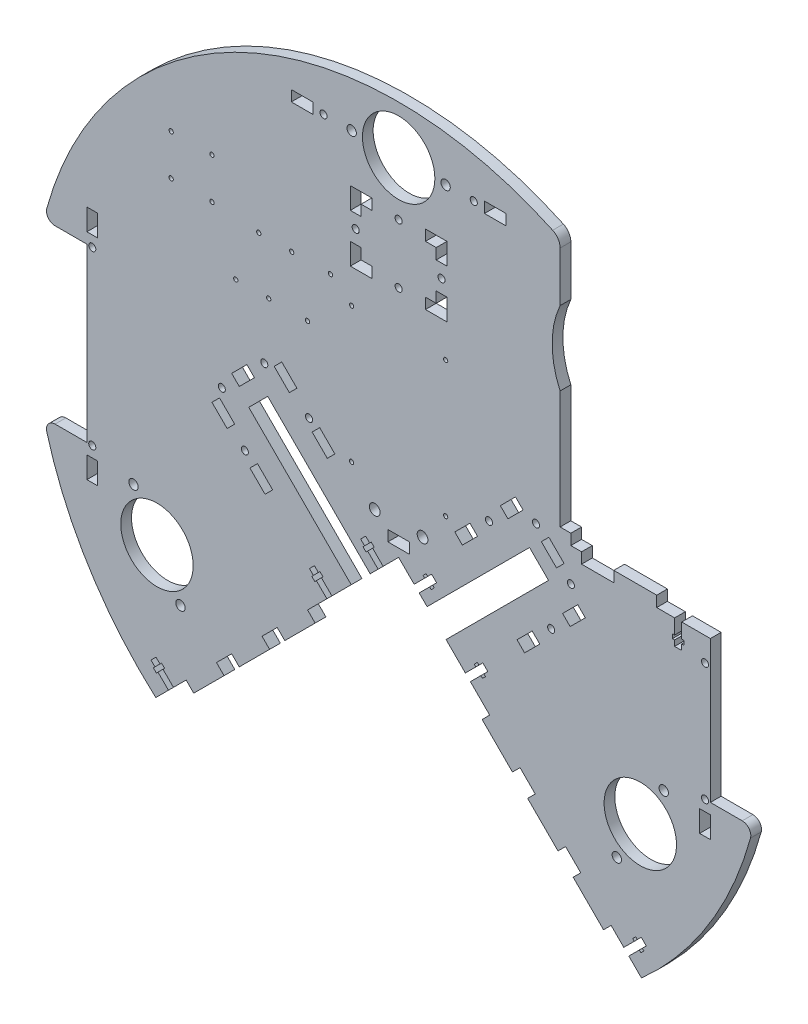
SolidWorks part; units mm, degrees
ref_plane "Front Plane" through (0, 0, 0) normal (0, 0, 1) x (1, 0, 0)
ref_plane "Top Plane" through (0, 0, 0) normal (0, 1, 0) x (1, 0, 0)
ref_plane "Right Plane" through (0, 0, 0) normal (1, 0, 0) x (0, 0, -1)
sketch "Sketch1" plane through (0, 0, 0) normal (0, 0, 1) x (1, 0, 0)
  circle A0 centre (0, 0) radius 215.9
  dimension "D1" = 431.8
extrude "Base Plate Extrusion" add sketch "Sketch1" along normal blind 6.35
sketch "Sketch2" plane through (0, 0, 6.35) normal (0, 0, 1) x (1, 0, 0)
  line L0 (0, 0) -> (0, -230.9791) construction
  line L1 (0, -17.4608) -> (143.6841, -161.1449)
  line L2 (0, -17.4608) -> (-143.6841, -161.1449)
  circle A1 centre (0, 0) radius 215.9 construction
  arc A2 (143.6841, -161.1449) -> (-143.6841, -161.1449) centre (0, 0) cw
  dimension "D1" = 90
  dimension "D2" = 203.2
extrude "V Funnel Cut" cut sketch "Sketch2" against normal through all
sketch "Sketch3" plane through (0, 0, 6.35) normal (0, 0, 1) x (1, 0, 0)
  line L0 (0, 0) -> (251.7982, 0) construction
  line L1 (209.8384, 50.8) -> (184.4384, 50.8)
  line L2 (209.8384, 50.8) -> (209.8384, -50.8)
  line L3 (209.8384, -50.8) -> (184.4384, -50.8)
  line L4 (184.4384, 50.8) -> (184.4384, -50.8)
  arc A0 (143.6841, -161.1449) -> (-143.6841, -161.1449) centre (0, 0) ccw construction
  arc A1 (209.8384, 50.8) -> (209.8384, -50.8) centre (0, 0) cw
  arc M7 (143.6841, -161.1449) -> (-143.6841, -161.1449) centre (0, 0) ccw
  dimension "D1" = 25.4
  dimension "D2" = 101.6
extrude "Wheel Track Cut" cut sketch "Sketch3" against normal through all contours L2 L0 A1 | L4 L0 L2 L1 | L0 L4 L3 L2 | L0 L2 M7 region at (197.1384, 25.4, 6.35) region at (197.1384, -25.4, 6.35) region at (212.266, 19.0862, 6.35) region at (212.266, -19.0862, 6.35)
mirror "Wheel Track Cut Mirror" about plane through (0, 0, 0) normal (1, 0, 0) of "Wheel Track Cut"
sketch "Sketch4" plane through (0, 0, 6.35) normal (0, 0, 1) x (1, 0, 0)
  line L0 (88.68, 15.0926) -> (77.4547, 26.3179)
  line L1 (88.68, 15.0926) -> (28.0633, -45.5241)
  line L2 (77.4547, 26.3179) -> (16.838, -34.2988)
  line L3 (28.0633, -45.5241) -> (16.838, -34.2988)
  line L4 (84.3174, 21.9553) -> (56.956, -5.4061) construction
  line L5 (65.1069, -1.7454) -> (69.5826, 2.7303) construction
  line L6 (65.0924, 7.2204) -> (60.6167, 2.7447) construction
  line L7 (143.6841, -161.1449) -> (0, -17.4608) construction
  dimension "D1" = 15.875
  dimension "D2" = 85.725
extrude "Silo Picker Clearance" cut sketch "Sketch4" against normal through all
sketch "Sketch5" plane through (0, 0, 6.35) normal (0, 0, 1) x (1, 0, 0)
  line L0 (-4.4901, -21.951) -> (0, -17.4608)
  line L1 (-4.4901, -21.951) -> (0, -26.4411)
  line L2 (0, -17.4608) -> (4.4901, -21.951)
  line L3 (0, -26.4411) -> (4.4901, -21.951)
  line L4 (0, -17.4608) -> (-143.6841, -161.1449) construction
  line L6 (4.4901, -21.951) -> (0, -26.4411) construction
  dimension "D1" = 6.35
extrude "V Funnel Corner" add sketch "Sketch5" against normal up to surface (6.35 mm away) up to face at (14.0691, -14.8765, 0)
mirror "Dump Picker Clearance" about plane through (0, 0, 0) normal (1, 0, 0) of "Silo Picker Clearance"
sketch "Sketch6" plane through (8.7304, -8.7304, 0) normal (0.7071, -0.7071, 0) x (0, 0, -1)
  line L0 (-6.35, -52.0342) -> (-6.35, -215.5467) construction
  line L1 (-6.35, -190.1467) -> (0, -190.1467)
  line L2 (-6.35, -190.1467) -> (-6.35, -164.7467)
  line L3 (-6.35, -164.7467) -> (0, -164.7467)
  line L4 (0, -190.1467) -> (0, -164.7467)
  line L5 (0, -52.0342) -> (0, -215.5467) construction
  dimension "D1" = 25.4
  dimension "D2" = 25.4
extrude "V Funnel Tab Left" add sketch "Sketch6" along normal blind 6.35
pattern_linear "V Funnel Tab Pattern Left" count 3 spacing 38.1 along (0.7071, 0.7071, 0) of "V Funnel Tab Left"
sketch "Sketch7" plane through (-8.7304, -8.7304, 0) normal (-0.7071, -0.7071, 0) x (0, 0, 1)
  line L0 (6.35, -215.5467) -> (6.35, -52.0342) construction
  line L1 (6.35, -164.7467) -> (0, -164.7467)
  line L2 (6.35, -164.7467) -> (6.35, -190.1467)
  line L3 (6.35, -190.1467) -> (0, -190.1467)
  line L4 (0, -164.7467) -> (0, -190.1467)
  line L5 (0, -215.5467) -> (0, -52.0342) construction
  dimension "D1" = 25.4
  dimension "D2" = 25.4
extrude "V Funnel Tab Right" add sketch "Sketch7" along normal blind 6.35
pattern_linear "V Funnel Tab Pattern Right" count 3 spacing 38.1 along (-0.7071, 0.7071, 0) of "V Funnel Tab Right"
sketch "Sketch8" plane through (0, 0, 0) normal (0, 0, -1) x (-1, 0, 0)
  line L0 (-70.046, -24.645) -> (-79.0263, -15.6648)
  line L1 (-79.0263, -15.6648) -> (-83.5164, -20.1549)
  line L2 (-83.5164, -20.1549) -> (-74.5361, -29.1352)
  line L3 (-74.5361, -29.1352) -> (-70.046, -24.645)
  line L4 (-96.9868, 2.2957) -> (-101.4769, -2.1944)
  line L5 (-101.4769, -2.1944) -> (-110.4572, 6.7859)
  line L6 (-110.4572, 6.7859) -> (-105.967, 11.276)
  line L7 (-105.967, 11.276) -> (-96.9868, 2.2957)
  line L8 (-97.8965, 28.3267) -> (-88.9163, 37.307)
  line L9 (-88.9163, 37.307) -> (-84.4262, 32.8169)
  line L10 (-84.4262, 32.8169) -> (-93.4064, 23.8366)
  line L11 (-93.4064, 23.8366) -> (-97.8965, 28.3267)
  line L12 (-64.6578, 34.6246) -> (-60.1677, 39.1148)
  line L13 (-60.1677, 39.1148) -> (-69.148, 48.095)
  line L14 (-69.148, 48.095) -> (-73.6381, 43.6049)
  line L15 (-73.6381, 43.6049) -> (-64.6578, 34.6246)
  line L16 (-46.6973, 16.6641) -> (-42.2072, 21.1543)
  line L17 (-42.2072, 21.1543) -> (-33.2269, 12.174)
  line L18 (-33.2269, 12.174) -> (-37.7171, 7.6839)
  line L19 (-37.7171, 7.6839) -> (-46.6973, 16.6641)
  line L20 (-105.967, 11.276) -> (-110.4572, 6.7859) construction
  line L21 (-69.148, 48.095) -> (-73.6381, 43.6049) construction
extrude "Silo Arm Tab Holes" cut sketch "Sketch8" against normal blind 6.35
sketch "Sketch10" plane through (0, 0, 0) normal (0, 0, -1) x (-1, 0, 0)
  line L0 (51.1875, 21.1543) -> (42.2072, 12.174)
  line L1 (42.2072, 12.174) -> (37.7171, 16.6641)
  line L2 (37.7171, 16.6641) -> (46.6973, 25.6444)
  line L3 (46.6973, 25.6444) -> (51.1875, 21.1543)
  line L4 (64.6578, 34.6246) -> (60.1677, 39.1148)
  line L5 (60.1677, 39.1148) -> (69.148, 48.095)
  line L6 (69.148, 48.095) -> (73.6381, 43.6049)
  line L7 (73.6381, 43.6049) -> (64.6578, 34.6246)
  line L8 (89.8026, 36.4207) -> (85.3124, 31.9306)
  line L9 (85.3124, 31.9306) -> (94.2927, 22.9503)
  line L10 (94.2927, 22.9503) -> (98.7828, 27.4404)
  line L11 (98.7828, 27.4404) -> (89.8026, 36.4207)
  line L12 (105.967, 11.276) -> (96.9868, 2.2957)
  line L13 (96.9868, 2.2957) -> (101.4769, -2.1944)
  line L14 (101.4769, -2.1944) -> (110.4572, 6.7859)
  line L15 (110.4572, 6.7859) -> (105.967, 11.276)
  line L16 (88.0065, -15.6648) -> (83.5164, -11.1747)
  line L17 (83.5164, -11.1747) -> (74.5361, -20.1549)
  line L18 (74.5361, -20.1549) -> (79.0263, -24.645)
  line L19 (79.0263, -24.645) -> (88.0065, -15.6648)
  line L20 (37.7171, 16.6641) -> (42.2072, 12.174) construction
  line L21 (74.5361, -20.1549) -> (79.0263, -24.645) construction
extrude "Dump Arm Tab Holes" cut sketch "Sketch10" against normal blind 6.35
sketch "Sketch11" plane through (0, 0, 0) normal (0, 0, -1) x (-1, 0, 0)
  line L1 (184.4384, -69.85) -> (178.0884, -69.85)
  line L2 (184.4384, -69.85) -> (184.4384, -57.15)
  line L3 (184.4384, -57.15) -> (178.0884, -57.15)
  line L4 (178.0884, -69.85) -> (178.0884, -57.15)
  line L5 (184.4384, 57.15) -> (178.0884, 57.15)
  line L6 (184.4384, 57.15) -> (184.4384, 69.85)
  line L7 (184.4384, 69.85) -> (178.0884, 69.85)
  line L8 (178.0884, 57.15) -> (178.0884, 69.85)
  line L9 (-178.0884, -69.85) -> (-184.4384, -69.85)
  line L10 (-178.0884, -69.85) -> (-178.0884, -57.15)
  line L11 (-178.0884, -57.15) -> (-184.4384, -57.15)
  line L12 (-184.4384, -69.85) -> (-184.4384, -57.15)
  line L13 (-178.0884, 57.15) -> (-184.4384, 57.15)
  line L14 (-178.0884, 57.15) -> (-178.0884, 69.85)
  line L15 (-178.0884, 69.85) -> (-184.4384, 69.85)
  line L16 (-184.4384, 57.15) -> (-184.4384, 69.85)
extrude "Wheel Support Tab Holes" cut sketch "Sketch11" against normal blind 6.35
sketch "Sketch13" plane through (0, 0, 6.35) normal (0, 0, 1) x (1, 0, 0)
  circle A0 centre (0, 187.325) radius 21.4313
  circle A1 centre (27.7812, 187.325) radius 2.7781
  circle A2 centre (-27.7813, 187.325) radius 2.7781
  dimension "D1" = 42.8625
  dimension "D2" = 5.5562
extrude "Caster Wheel Hole" cut sketch "Sketch13" against normal through all
sketch "Sketch14" plane through (0, 0, 6.35) normal (0, 0, 1) x (1, 0, 0)
  line L0 (184.4384, 48.6664) -> (178.0884, 52.9336) construction
  line L1 (184.4384, 50.8) -> (184.4384, -50.8) construction
  line L2 (178.0884, 48.6664) -> (184.4384, 48.6664) construction
  line L3 (184.4384, 52.9336) -> (178.0884, 48.6664) construction
  line L4 (184.4384, -52.9336) -> (178.0884, -48.6664) construction
  line L5 (184.4384, -48.6664) -> (178.0884, -52.9336) construction
  line L6 (178.0884, -48.6664) -> (184.4384, -48.6664) construction
  circle A0 centre (181.2634, 50.8) radius 2.0955
  circle A1 centre (181.2634, -50.8) radius 2.0955
  dimension "D1" = 4.191
extrude "Wheel Support Hole" cut sketch "Sketch14" against normal through all
mirror "Wheel Support Hole Mirror" about plane through (0, 0, 0) normal (1, 0, 0) of "Wheel Support Hole"
sketch "Sketch15" plane through (0, 0, 6.35) normal (0, 0, 1) x (1, 0, 0)
  line L0 (-134.7038, -152.1647) -> (-152.6084, -134.2601) construction
  line L1 (-125.7236, -143.1844) -> (-143.6841, -161.1449) construction
  line L2 (-40.9724, -58.4333) -> (-60.7132, -38.6924) construction
  line L3 (-28.0633, -45.5241) -> (-53.8815, -71.3424) construction
  line L4 (-10.6641, -28.1249) -> (-27.2834, -11.5055) construction
  line L5 (-4.4901, -21.951) -> (-16.838, -34.2988) construction
  line B0 (-136.1856, -153.6464) -> (-133.2221, -150.6829)
  line B1 (-141.2145, -142.6905) -> (-140.2716, -141.7476)
  line B2 (-140.2716, -141.7476) -> (-138.4755, -143.5436)
  line B3 (-138.4755, -143.5436) -> (-139.4185, -144.4866)
  line B4 (-139.4185, -144.4866) -> (-133.2221, -150.6829)
  line B5 (-141.2145, -142.6905) -> (-143.5494, -140.3556)
  line B6 (-143.5494, -140.3556) -> (-146.5129, -143.3191)
  line B7 (-144.178, -145.654) -> (-146.5129, -143.3191)
  line B8 (-142.382, -147.45) -> (-136.1856, -153.6464)
  line B9 (-143.3249, -148.393) -> (-142.382, -147.45)
  line B10 (-145.1209, -146.5969) -> (-143.3249, -148.393)
  line B11 (-144.178, -145.654) -> (-145.1209, -146.5969)
  line B12 (-42.4542, -59.915) -> (-39.4907, -56.9515)
  line B13 (-47.4831, -48.9591) -> (-46.5402, -48.0162)
  line B14 (-46.5402, -48.0162) -> (-44.7441, -49.8122)
  line B15 (-44.7441, -49.8122) -> (-45.6871, -50.7551)
  line B16 (-45.6871, -50.7551) -> (-39.4907, -56.9515)
  line B17 (-47.4831, -48.9591) -> (-49.818, -46.6242)
  line B18 (-49.818, -46.6242) -> (-52.7815, -49.5877)
  line B19 (-50.4466, -51.9226) -> (-52.7815, -49.5877)
  line B20 (-48.6505, -53.7186) -> (-42.4542, -59.915)
  line B21 (-49.5935, -54.6615) -> (-48.6505, -53.7186)
  line B22 (-51.3895, -52.8655) -> (-49.5935, -54.6615)
  line B23 (-50.4466, -51.9226) -> (-51.3895, -52.8655)
  line B24 (-12.1458, -29.6066) -> (-9.1823, -26.6431)
  line B25 (-17.1747, -18.6507) -> (-16.2318, -17.7078)
  line B26 (-16.2318, -17.7078) -> (-14.4358, -19.5038)
  line B27 (-14.4358, -19.5038) -> (-15.3787, -20.4468)
  line B28 (-15.3787, -20.4468) -> (-9.1823, -26.6431)
  line B29 (-17.1747, -18.6507) -> (-19.5096, -16.3159)
  line B30 (-19.5096, -16.3159) -> (-22.4731, -19.2793)
  line B31 (-20.1382, -21.6142) -> (-22.4731, -19.2793)
  line B32 (-18.3422, -23.4103) -> (-12.1458, -29.6066)
  line B33 (-19.2851, -24.3532) -> (-18.3422, -23.4103)
  line B34 (-21.0812, -22.5571) -> (-19.2851, -24.3532)
  line B35 (-20.1382, -21.6142) -> (-21.0812, -22.5571)
sketch_block_instance "TSlot-1"
sketch_block "TSlot" parameters "D1"=3.302, "D2"=2.54, "D3"=3.175, "D4"=8.763, "D5"=1.3462
sketch_block_instance "TSlot-3"
sketch_block_instance "TSlot-4"
extrude "V Funnel T Slot Cut Out" cut sketch "Sketch15" against normal through all
mirror "V Funnel T Slot Cut Out Mirror" about plane through (0, 0, 0) normal (1, 0, 0) of "V Funnel T Slot Cut Out"
sketch "Sketch19" plane through (0, 0, 6.35) normal (0, 0, 1) x (1, 0, 0)
  line L0 (46.5836, 190.5) -> (42.3164, 184.15) construction
  line L1 (46.5836, 184.15) -> (42.3164, 190.5) construction
  line L2 (-42.3164, 190.5) -> (-46.5836, 184.15) construction
  line L3 (-42.3164, 184.15) -> (-46.5836, 190.5) construction
  circle A0 centre (44.45, 187.325) radius 2.0955
  circle A1 centre (-44.45, 187.325) radius 2.0955
  dimension "D1" = 4.191
extrude "Switch Plate Holes" cut sketch "Sketch19" against normal through all
sketch "Sketch20" plane through (0, 0, 0) normal (0, 0, -1) x (-1, 0, 0)
  line L1 (-50.8, 184.15) -> (-63.5, 184.15)
  line L2 (-50.8, 184.15) -> (-50.8, 190.5)
  line L3 (-50.8, 190.5) -> (-63.5, 190.5)
  line L4 (-63.5, 184.15) -> (-63.5, 190.5)
  line L5 (63.5, 184.15) -> (50.8, 184.15)
  line L6 (63.5, 184.15) -> (63.5, 190.5)
  line L7 (63.5, 190.5) -> (50.8, 190.5)
  line L8 (50.8, 184.15) -> (50.8, 190.5)
extrude "Swith Plate Tab Holes" cut sketch "Sketch20" against normal through all
sketch "Sketch26" plane through (0, 0, 6.35) normal (0, 0, 1) x (1, 0, 0)
  line L0 (89.5152, -5.1758) -> (90.988, -12.6833) construction
  line L1 (86.4978, -8.1932) -> (94.0053, -9.666) construction
  line L2 (52.6961, 31.6432) -> (54.1689, 24.1357) construction
  line L3 (49.6788, 28.6258) -> (57.1863, 27.1531) construction
  line L4 (105.6855, 20.5377) -> (98.178, 19.065) construction
  line L5 (102.6682, 23.5551) -> (101.1954, 16.0476) construction
  line L6 (82.0136, 44.2097) -> (80.5408, 36.7022) construction
  line L7 (85.0309, 41.1923) -> (77.5234, 39.7196) construction
  circle A0 centre (90.2516, -8.9296) radius 2.0955
  circle A1 centre (53.4325, 27.8895) radius 2.0955
  circle A2 centre (101.9318, 19.8014) radius 2.0955
  circle A3 centre (81.2772, 40.4559) radius 2.0955
  dimension "D1" = 4.191
extrude "Silo Arm Holes" cut sketch "Sketch26" against normal through all
sketch "Sketch27" plane through (0, 0, 6.35) normal (0, 0, 1) x (1, 0, 0)
  line L0 (-49.2298, 28.1768) -> (-56.7373, 26.7041) construction
  line L1 (-52.2471, 31.1942) -> (-53.7199, 23.6867) construction
  line L2 (-80.2116, 46.0116) -> (-78.7389, 38.5041) construction
  line L3 (-83.229, 42.9942) -> (-75.7215, 41.5215) construction
  line L4 (-105.3564, 20.8669) -> (-103.8836, 13.3594) construction
  line L5 (-108.3737, 17.8495) -> (-100.8662, 16.3768) construction
  line L6 (-94.6968, -8.9745) -> (-87.2432, -7.4479) construction
  line L7 (-91.7333, -11.938) -> (-90.2067, -4.4844) construction
  circle A0 centre (-52.9835, 27.4404) radius 2.0955
  circle A1 centre (-79.4753, 42.2579) radius 2.0955
  circle A2 centre (-104.62, 17.1131) radius 2.0955
  circle A3 centre (-90.97, -8.2112) radius 2.0955
  dimension "D1" = 4.191
extrude "Dump Arm Holes" cut sketch "Sketch27" against normal through all
fillet "Wheel Slot Fillet" radius 5.08 4 edges at (209.8384, -50.8, 3.175) (209.8384, 50.8, 3.175) (-209.8384, -50.8, 3.175) (-209.8384, 50.8, 3.175)
sketch "Sketch28" plane through (0, 0, 6.35) normal (0, 0, 1) x (1, 0, 0)
  line L0 (0, 0) -> (0, 258.9974) construction
  line L1 (0, 0) -> (249.4479, -144.0188) construction
  line L2 (0, 0) -> (-249.719, -144.1753) construction
  line L3 (-142.9808, -82.55) -> (-156.8714, -58.4907) construction
  line L4 (-27.7813, 187.325) -> (0, 187.325) construction
  line L5 (-142.9808, -82.55) -> (-129.0902, -106.6093) construction
  circle A0 centre (-142.9808, -82.55) radius 21.4313
  circle A1 centre (0, 187.325) radius 21.4313 construction
  circle A2 centre (-156.8714, -58.4907) radius 2.7781
  circle A3 centre (-27.7813, 187.325) radius 2.7781 construction
  circle A4 centre (-129.0902, -106.6093) radius 2.7781
  dimension "D1" = 120
  dimension "D2" = 120
  dimension "D3" = 165.1
extrude "Front Caster Holes" cut sketch "Sketch28" against normal through all
mirror "Front Caster Hole Mirror" about plane through (0, 0, 0) normal (1, 0, 0) of "Front Caster Holes"
sketch "Gyro Holes" plane through (0, 0, 6.35) normal (0, 0, 1) x (1, 0, 0)
  line L1 (-134.5682, 109.4626) -> (-110.4382, 109.4626) construction
  line L2 (-134.5682, 109.4626) -> (-134.5682, 133.5926) construction
  line L3 (-134.5682, 133.5926) -> (-110.4382, 133.5926) construction
  line L4 (-110.4382, 109.4626) -> (-110.4382, 133.5926) construction
  line L5 (-134.5682, 109.4626) -> (-110.4382, 133.5926) construction
  line L6 (-134.5682, 133.5926) -> (-110.4382, 109.4626) construction
  circle A0 centre (-134.5682, 133.5926) radius 1.27
  circle A1 centre (-110.4382, 133.5926) radius 1.27
  circle A2 centre (-110.4382, 109.4626) radius 1.27
  circle A3 centre (-134.5682, 109.4626) radius 1.27
  point P0 (-122.5032, 121.5276)
  dimension "D2" = 24.13
  dimension "D1" = 2.54
extrude "GyroHoles" cut sketch "Gyro Holes" against normal through all
sketch "MotorControllerHoleSketch" plane through (0, 0, 6.35) normal (0, 0, 1) x (1, 0, 0)
  line L0 (0, 215.9) -> (0, -26.4411) construction
  line L2 (-27.82, 17.5746) -> (27.82, 17.5746) construction
  line L3 (-27.82, 17.5746) -> (-27.82, 97.6146) construction
  line L4 (-27.82, 97.6146) -> (27.82, 97.6146) construction
  line L5 (27.82, 17.5746) -> (27.82, 97.6146) construction
  line L6 (-27.82, 17.5746) -> (27.82, 97.6146) construction
  line L7 (-27.82, 97.6146) -> (27.82, 17.5746) construction
  arc A0 (208.1777, 57.2265) -> (-208.1777, 57.2265) centre (0, 0) ccw construction
  circle A1 centre (-27.82, 97.6146) radius 1.25
  circle A2 centre (27.82, 97.6146) radius 1.25
  circle A3 centre (27.82, 17.5746) radius 1.25
  circle A4 centre (-27.82, 17.5746) radius 1.25
  point P6 (0, 57.5946)
  dimension "D1" = 2.5
  dimension "D2" = 55.64
  dimension "D3" = 80.04
extrude "Motor Controller Hole" cut sketch "MotorControllerHoleSketch" against normal through all
sketch "Sketch31" plane through (0, 0, 6.35) normal (0, 0, 1) x (1, 0, 0)
  line L0 (-58.5988, 118.6025) -> (-58.5988, 61.2016) construction
  line L1 (-40.3087, 76.7541) -> (-53.9191, 76.7541) construction
  line L2 (-40.3087, 76.7541) -> (-40.3087, 107.5065) construction
  line L3 (-40.3087, 107.5065) -> (-53.9191, 107.5065) construction
  line L4 (-53.9191, 76.7541) -> (-53.9191, 107.5065) construction
  line L5 (-40.3087, 76.7541) -> (-53.9191, 107.5065) construction
  line L6 (-40.3087, 107.5065) -> (-53.9191, 76.7541) construction
  line L7 (-63.2785, 76.7541) -> (-76.8888, 76.7541) construction
  line L8 (-63.2785, 76.7541) -> (-63.2785, 107.5065) construction
  line L9 (-63.2785, 107.5065) -> (-76.8888, 107.5065) construction
  line L10 (-76.8888, 76.7541) -> (-76.8888, 107.5065) construction
  line L11 (-63.2785, 76.7541) -> (-76.8888, 107.5065) construction
  line L12 (-63.2785, 107.5065) -> (-76.8888, 76.7541) construction
  line L13 (-70.0836, 92.1303) -> (-47.1139, 92.1303) construction
  line L15 (-82.7354, 76.7541) -> (-96.3457, 76.7541) construction
  line L16 (-82.7354, 76.7541) -> (-82.7354, 107.5065) construction
  line L17 (-82.7354, 107.5065) -> (-96.3457, 107.5065) construction
  line L18 (-96.3457, 76.7541) -> (-96.3457, 107.5065) construction
  line L19 (-82.7354, 76.7541) -> (-96.3457, 107.5065) construction
  line L20 (-82.7354, 107.5065) -> (-96.3457, 76.7541) construction
  circle A0 centre (-76.8888, 76.7541) radius 1.27
  circle A1 centre (-63.2785, 107.5065) radius 1.27
  circle A2 centre (-53.9191, 76.7541) radius 1.27
  circle A3 centre (-40.3087, 107.5065) radius 1.27
  circle A4 centre (-82.7354, 107.5065) radius 1.27
  circle A5 centre (-96.3457, 76.7541) radius 1.27
  point P0 (-47.1139, 92.1303)
  point P5 (-70.0836, 92.1303)
  point P18 (-89.5406, 92.1303)
  dimension "D1" = 2.54
  dimension "D2" = 33.6296
extrude "BuckConverterHoles" cut sketch "Sketch31" against normal through all
sketch "Sketch34" plane through (0, 0, 0) normal (0, 0, -1) x (-1, 0, 0)
  line L1 (-28.575, 158.75) -> (-15.875, 158.75)
  line L2 (-28.575, 158.75) -> (-28.575, 152.4)
  line L3 (-22.225, 152.4) -> (-15.875, 152.4)
  line L4 (-15.875, 158.75) -> (-15.875, 152.4)
  line L5 (15.875, 158.75) -> (28.575, 158.75)
  line L6 (15.875, 158.75) -> (15.875, 152.4)
  line L7 (15.875, 152.4) -> (22.225, 152.4)
  line L8 (28.575, 158.75) -> (28.575, 152.4)
  line L9 (15.875, 123.825) -> (22.225, 123.825)
  line L10 (15.875, 123.825) -> (15.875, 117.475)
  line L11 (15.875, 117.475) -> (28.575, 117.475)
  line L12 (28.575, 123.825) -> (28.575, 117.475)
  line L13 (-22.225, 123.825) -> (-15.875, 123.825)
  line L14 (-28.575, 123.825) -> (-28.575, 117.475)
  line L15 (-28.575, 117.475) -> (-15.875, 117.475)
  line L16 (-15.875, 123.825) -> (-15.875, 117.475)
  line L17 (-28.575, 130.175) -> (-22.225, 130.175)
  line L18 (-28.575, 130.175) -> (-28.575, 123.825)
  line L20 (-22.225, 130.175) -> (-22.225, 123.825)
  line L22 (-28.575, 152.4) -> (-28.575, 146.05)
  line L23 (-28.575, 146.05) -> (-22.225, 146.05)
  line L24 (-22.225, 152.4) -> (-22.225, 146.05)
  line L26 (22.225, 152.4) -> (22.225, 146.05)
  line L27 (22.225, 146.05) -> (28.575, 146.05)
  line L28 (28.575, 152.4) -> (28.575, 146.05)
  line L29 (22.225, 130.175) -> (28.575, 130.175)
  line L30 (22.225, 130.175) -> (22.225, 123.825)
  line L32 (28.575, 130.175) -> (28.575, 123.825)
extrude "Cut-Extrude6" cut sketch "Sketch34" against normal through all
sketch "Sketch35" plane through (0, 0, 6.35) normal (0, 0, 1) x (1, 0, 0)
  line L0 (-22.225, 136.017) -> (-28.575, 140.208) construction
  line L1 (-28.575, 136.017) -> (-22.225, 140.208) construction
  line L2 (-2.0955, 152.4) -> (2.0955, 158.75) construction
  line L3 (2.0955, 152.4) -> (-2.0955, 158.75) construction
  line L4 (22.225, 136.017) -> (28.575, 140.208) construction
  line L5 (22.225, 140.208) -> (28.575, 136.017) construction
  line L6 (2.0955, 123.825) -> (-2.0955, 117.475) construction
  line L7 (-2.0955, 123.825) -> (2.0955, 117.475) construction
  circle A0 centre (0, 120.65) radius 2.0955
  circle A1 centre (25.4, 138.1125) radius 2.0955
  circle A2 centre (0, 155.575) radius 2.0955
  circle A3 centre (-25.4, 138.1125) radius 2.0955
  dimension "D1" = 4.191
extrude "Cut-Extrude7" cut sketch "Sketch35" against normal through all
sketch "Sketch37" [suppressed] plane through (0, 0, 0) normal (0, 0, -1) x (-1, 0, 0)
  line L0 (-86.0134, 49.1901) -> (-174.9134, 49.1901) construction
  line L1 (-117.7634, 49.1901) -> (-143.1634, 49.1901)
  line L2 (-117.7634, 49.1901) -> (-117.7634, 55.5401)
  line L3 (-117.7634, 55.5401) -> (-143.1634, 55.5401)
  line L4 (-143.1634, 49.1901) -> (-143.1634, 55.5401)
  line L5 (-117.7634, 49.1901) -> (-117.7634, 55.5401) construction
sketch "Sketch41" plane through (0, 0, 6.35) normal (0, 0, 1) x (1, 0, 0)
  line L0 (95.5384, 193.611) -> (95.5384, 45.8763)
  line L1 (95.5384, 33.1763) -> (95.5384, -193.611) construction
  line L2 (95.5384, 45.8763) -> (101.8884, 45.8763)
  line L3 (101.8884, 45.8763) -> (101.8884, 39.5263)
  line L4 (101.8884, 39.5263) -> (108.2384, 39.5263)
  line L5 (108.2384, 39.5263) -> (108.2384, 33.1763)
  line L6 (108.2384, 33.1763) -> (218.8605, 33.1763)
  line L7 (218.8605, 33.1763) -> (218.8605, 193.611)
  line L8 (218.8605, 193.611) -> (95.5384, 193.611)
  arc A0 (208.1777, 57.2265) -> (-208.1777, 57.2265) centre (0, 0) ccw construction
extrude "Cut-Extrude13" cut sketch "Sketch41" against normal through all
fillet "Fillet1" radius 7.62 1 edges at (95.5384, 193.611, 3.175)
sketch "Sketch42" plane through (0, 0, 6.35) normal (0, 0, 1) x (1, 0, 0)
  line L0 (95.5384, 159.3081) -> (95.5384, 115.5739)
  line L1 (95.5384, 188.8145) -> (95.5384, 45.8763) construction
  arc A1 (95.5384, 115.5739) -> (95.5384, 159.3081) centre (143.7787, 137.441) cw
extrude "Cut-Extrude14" cut sketch "Sketch42" against normal through all
sketch "Sketch44" plane through (0, 33.1763, 0) normal (0, 1, 0) x (1, 0, 0)
  line L0 (108.2384, -6.35) -> (184.4384, -6.35) construction
  line L1 (127.2884, -6.35) -> (152.6884, -6.35)
  line L2 (127.2884, -6.35) -> (127.2884, 0)
  line L3 (127.2884, 0) -> (152.6884, 0)
  line L4 (152.6884, -6.35) -> (152.6884, 0)
  line L5 (108.2384, 0) -> (184.4384, 0) construction
extrude "Boss-Extrude2" add sketch "Sketch44" along normal blind 6.35
sketch "Sketch45" plane through (0, 0, 6.35) normal (0, 0, 1) x (1, 0, 0)
  line L0 (152.6884, 33.1763) -> (184.4384, 33.1763) construction
  line L1 (163.2929, 39.5263) -> (163.2929, 33.1763) construction
  line B0 (167.4839, 33.1763) -> (163.2929, 33.1763)
  line B1 (163.2929, 21.8733) -> (161.9594, 21.8733)
  line B2 (161.9594, 21.8733) -> (161.9594, 24.4133)
  line B3 (161.9594, 24.4133) -> (163.2929, 24.4133)
  line B4 (163.2929, 24.4133) -> (163.2929, 33.1763)
  line B5 (163.2929, 21.8733) -> (163.2929, 18.5713)
  line B6 (163.2929, 18.5713) -> (167.4839, 18.5713)
  line B7 (167.4839, 21.8733) -> (167.4839, 18.5713)
  line B8 (167.4839, 24.4133) -> (167.4839, 33.1763)
  line B9 (168.8174, 24.4133) -> (167.4839, 24.4133)
  line B10 (168.8174, 21.8733) -> (168.8174, 24.4133)
  line B11 (167.4839, 21.8733) -> (168.8174, 21.8733)
  line B12 (165.3884, 33.1763) -> (165.3884, 18.5713) construction
  line B13 (161.9594, 23.1433) -> (172.0532, 23.1433) construction
sketch_block_instance "TSlot-7"
extrude "Cut-Extrude15" cut sketch "Sketch45" against normal through all
sketch "Sketch47" plane through (0, 0, 0) normal (0, 0, -1) x (-1, 0, 0)
  line L1 (-6.35, -12.6983) -> (6.35, -12.6983)
  line L2 (-6.35, -12.6983) -> (-6.35, -6.3483)
  line L3 (-6.35, -6.3483) -> (6.35, -6.3483)
  line L4 (6.35, -12.6983) -> (6.35, -6.3483)
extrude "Cut-Extrude16" cut sketch "Sketch47" against normal through all
extrude "Boss-Extrude1" [suppressed] add sketch "Sketch37" against normal up to surface (6.35 mm away) up to face at (0, -9.5233, 6.35)
sketch "Sketch38" plane through (0, 0, 0) normal (0, 0, -1) x (-1, 0, 0)
  line L2 (-186.392, 104.3946) -> (-275.292, 104.3946) construction
  line L4 (-143.1634, 55.5401) -> (-143.1634, 49.1901) construction
  line L5 (-268.942, 186.9446) -> (-268.942, 110.7446) construction
  line L7 (-192.742, 110.7446) -> (-192.742, 186.9446) construction
  line L8 (-117.7634, 49.1901) -> (-117.7634, 55.5401) construction
  line B0 (-153.1572, 104.3946) -> (-157.3482, 104.3946)
  line B1 (-157.3482, 93.0916) -> (-158.6817, 93.0916)
  line B2 (-158.6817, 93.0916) -> (-158.6817, 95.6316)
  line B3 (-158.6817, 95.6316) -> (-157.3482, 95.6316)
  line B4 (-157.3482, 95.6316) -> (-157.3482, 104.3946)
  line B5 (-157.3482, 93.0916) -> (-157.3482, 89.7896)
  line B6 (-157.3482, 89.7896) -> (-153.1572, 89.7896)
  line B7 (-153.1572, 93.0916) -> (-153.1572, 89.7896)
  line B8 (-153.1572, 95.6316) -> (-153.1572, 104.3946)
  line B9 (-151.8237, 95.6316) -> (-153.1572, 95.6316)
  line B10 (-151.8237, 93.0916) -> (-151.8237, 95.6316)
  line B11 (-153.1572, 93.0916) -> (-151.8237, 93.0916)
  line B12 (-155.2527, 104.3946) -> (-155.2527, 89.7896) construction
  line B13 (-203.9572, 104.3946) -> (-208.1482, 104.3946)
  line B14 (-208.1482, 93.0916) -> (-209.4817, 93.0916)
  line B15 (-209.4817, 93.0916) -> (-209.4817, 95.6316)
  line B16 (-209.4817, 95.6316) -> (-208.1482, 95.6316)
  line B17 (-208.1482, 95.6316) -> (-208.1482, 104.3946)
  line B18 (-208.1482, 93.0916) -> (-208.1482, 89.7896)
  line B19 (-208.1482, 89.7896) -> (-203.9572, 89.7896)
  line B20 (-203.9572, 93.0916) -> (-203.9572, 89.7896)
  line B21 (-203.9572, 95.6316) -> (-203.9572, 104.3946)
  line B22 (-202.6237, 95.6316) -> (-203.9572, 95.6316)
  line B23 (-202.6237, 93.0916) -> (-202.6237, 95.6316)
  line B24 (-203.9572, 93.0916) -> (-202.6237, 93.0916)
  line B25 (-206.0527, 104.3946) -> (-206.0527, 89.7896) construction
sketch_block_instance "TSlot-5"
sketch_block_instance "TSlot-6"
extrude "Cut-Extrude9" [suppressed] cut sketch "Sketch38" against normal through all
sketch "Sketch39" plane through (0, 0, 0) normal (0, 0, -1) x (-1, 0, 0)
  line L0 (-184.4384, 33.1763) -> (-227.6876, 33.1763)
  line L1 (-95.5384, 33.1763) -> (-184.4384, 33.1763)
  line L2 (-95.5384, 33.1763) -> (-95.5384, 122.0763)
  line L3 (-95.5384, 122.0763) -> (-184.4384, 122.0763)
  arc A0 (-227.6876, 33.1763) -> (-184.4384, 122.0763) centre (-22.9914, -11.4365) cw
extrude "Cut-Extrude11" cut sketch "Sketch39" against normal through all
sketch "Sketch40" plane through (0, 0, 6.35) normal (0, 0, 1) x (1, 0, 0)
  line L0 (178.0884, 21.1455) -> (184.4384, 16.9545) construction
  line L1 (184.4384, 33.1763) -> (184.4384, -50.8) construction
  line L2 (178.0884, 16.9545) -> (184.4384, 16.9545) construction
  line L3 (178.0884, 16.9545) -> (184.4384, 21.1455) construction
  circle A0 centre (181.2634, 19.05) radius 2.0955
  dimension "D1" = 4.191
extrude "Cut-Extrude12" cut sketch "Sketch40" against normal through all
sketch "Sketch48" plane through (0, 33.1763, 0) normal (0, 1, 0) x (1, 0, 0)
  line L0 (95.5384, 0) -> (163.2929, 0) construction
  line L1 (95.5384, -6.35) -> (108.2384, -6.35)
  line L2 (95.5384, -6.35) -> (95.5384, 0)
  line L3 (95.5384, 0) -> (108.2384, 0)
  line L4 (108.2384, -6.35) -> (108.2384, 0)
extrude "Boss-Extrude3" add sketch "Sketch48" along normal blind 6.35
sketch "Sketch49" plane through (95.5384, 0, 0) normal (1, 0, 0) x (0, 0, -1)
  line L0 (0, 115.5739) -> (0, 39.5263) construction
  line L1 (-6.35, 39.5263) -> (0, 39.5263)
  line L2 (-6.35, 39.5263) -> (-6.35, 45.8763)
  line L3 (-6.35, 45.8763) -> (0, 45.8763)
  line L4 (0, 39.5263) -> (0, 45.8763)
  line L5 (0, 45.8763) -> (-6.35, 45.8763) construction
extrude "Boss-Extrude4" add sketch "Sketch49" along normal blind 6.35
sketch "Sketch50" plane through (0, 0, 0) normal (0, 0, -1) x (-1, 0, 0)
  line L0 (0, -17.4608) -> (-4.4901, -21.951)
  line L1 (-4.4901, -21.951) -> (0, -26.4411)
  line L2 (0, -26.4411) -> (4.4901, -21.951)
  line L3 (4.4901, -21.951) -> (0, -17.4608)
extrude "Cut-Extrude17" cut sketch "Sketch50" against normal through all
sketch "Sketch51" plane through (0, 0, 0) normal (0, 0, -1) x (-1, 0, 0)
  line L0 (0, 0) -> (0, 11.938) construction
  circle A0 centre (14.1392, 0) radius 3.175
  circle A1 centre (-14.1392, 0) radius 3.175
  dimension "D1" = 6.35
extrude "Cut-Extrude18" cut sketch "Sketch51" against normal through all
sketch "Sketch52" plane through (0, 33.1763, 0) normal (0, 1, 0) x (1, 0, 0)
  line L0 (108.2384, -6.35) -> (163.2929, -6.35) construction
  line L1 (127.2884, -6.35) -> (152.6884, -6.35)
  line L2 (127.2884, -6.35) -> (127.2884, 0)
  line L3 (127.2884, 0) -> (152.6884, 0)
  line L4 (152.6884, -6.35) -> (152.6884, 0)
  line L5 (127.2884, -6.35) -> (127.2884, 0) construction
  line L6 (108.2384, 0) -> (163.2929, 0) construction
  line L7 (152.6884, -6.35) -> (152.6884, 0) construction
extrude "Boss-Extrude5" add sketch "Sketch52" along normal blind 6.35
